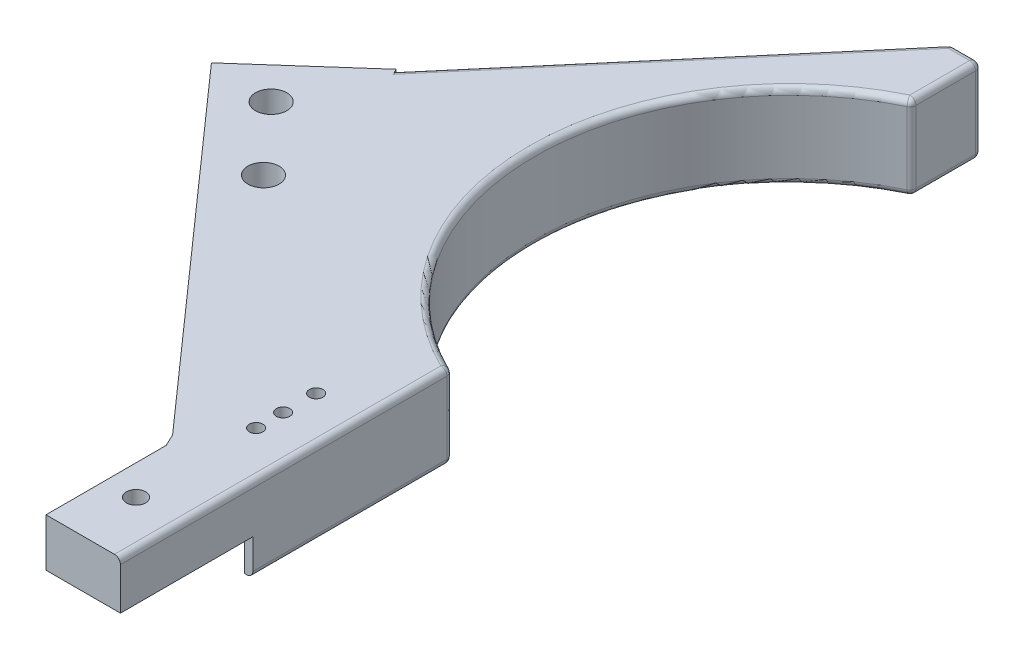
SolidWorks part; units mm, degrees
ref_plane "Front Plane" through (0, 0, 0) normal (0, 0, 1) x (1, 0, 0)
ref_plane "Top Plane" through (0, 0, 0) normal (0, 1, 0) x (1, 0, 0)
ref_plane "Right Plane" through (0, 0, 0) normal (1, 0, 0) x (0, 0, -1)
sketch "Sketch1" plane through (0, 0, 0) normal (0, 1, 0) x (1, 0, 0)
  line L0 (47.5, -78.4427) -> (47.5, -38.4427)
  line L1 (42.5, 50) -> (0, 0)
  line L2 (0, 0) -> (35.1, -73.4224)
  line L3 (47.5, 38.4427) -> (47.5, 50)
  line L4 (42.5, 50) -> (47.5, 50)
  line L6 (35.1, -73.4224) -> (35.1, -93.4427)
  line L8 (37.5, -78.4427) -> (37.5, -93.4427) construction
  line L9 (37.5, -93.4427) -> (47.5, -93.4427)
  line L10 (47.5, -78.4427) -> (47.5, -93.4427)
  line L11 (35.1, -93.4427) -> (37.5, -93.4427)
  line L12 (35.1, -73.4224) -> (37.5, -78.4427) construction
  arc A0 (47.5, 38.4427) -> (47.5, -38.4427) centre (65.622, 0) ccw
  dimension "D1" = 85
  dimension "D2" = 50
  dimension "D3" = 40
  dimension "D4" = 47.5
  dimension "D5" = 10
  dimension "D6" = 5
  dimension "D7" = 65.622
  dimension "D8" = 15
  dimension "D9" = 12.4
extrude "Boss-Extrude1" add sketch "Sketch1" along normal blind 14
sketch "Sketch3" plane through (0, 0, 0) normal (0, -1, 0) x (1, 0, 0)
  line L8 (36.1851, 83.429) -> (36.1851, 109.2435) construction
  line L9 (33.255, 84.4031) -> (36.1851, 92.429)
  line L10 (35.3457, 53.1123) -> (33.255, 84.4031)
  line L11 (46.1351, 70.029) -> (44.8209, 53.0622)
  line L12 (46.1351, 88.029) -> (46.1351, 70.029)
  line L13 (44.8851, 92.429) -> (46.1351, 88.029)
  line L14 (36.1851, 92.429) -> (44.8851, 92.429)
  circle A6 centre (40.0851, 83.429) radius 6.75 construction
  circle A7 centre (40.0851, 83.429) radius 4.125
  circle A8 centre (40.0851, 63.429) radius 1.5 construction
  circle A9 centre (40.0851, 58.929) radius 1.5 construction
  circle A10 centre (40.0851, 53.429) radius 1.5 construction
  arc A11 (44.8209, 53.0622) -> (35.3457, 53.1123) centre (40.0851, 53.429) cw
  point P48 (33.3351, 83.429)
  dimension "D6" = 108.929
  dimension "D7" = 113.429
  dimension "D1" = 3
  dimension "D2" = 40.0851
  dimension "D3" = 47.5
  dimension "D4" = 50
  dimension "D5" = 103.429
extrude "Cut-Extrude1" cut sketch "Sketch3" against normal blind 6
sketch "Sketch5" plane through (0, 6, 0) normal (0, -1, 0) x (1, 0, 0)
  circle A0 centre (40.0851, 63.429) radius 1.125
  circle A1 centre (40.0851, 58.929) radius 1.125
  circle A2 centre (40.0851, 53.429) radius 1.125
  circle A3 centre (40.0851, 63.429) radius 1.5 construction
  circle A4 centre (40.0851, 58.929) radius 1.5 construction
  circle A5 centre (40.0851, 53.429) radius 1.5 construction
  dimension "D1" = 2.25
extrude "Cut-Extrude2" cut sketch "Sketch5" against normal blind 15
fillet "Fillet1" radius 1 14 edges at (47.5, 7, 38.4427) (47.5, 7, -38.4427) (47.5, 7, -50) (42.5, 7, -50) (21.25, 14, -25) (45, 14, -50) (47.5, 14, -44.2214) (23.122, 14, 0) (47.5, 14, 65.9427) (21.25, 0, -25) (45, 0, -50) (47.5, 0, -44.2214) (23.122, 0, 0) (47.5, 0, 65.9427)
sketch "Sketch6" plane through (0, 0, 0) normal (0, -1, 0) x (1, 0, 0)
  line L0 (-40.4586, -20.0772) -> (-49.8876, -23.408)
  line L2 (0, 0) -> (34.1249, 71.3827)
  line L5 (-49.8876, -23.408) -> (34.1249, 71.3827)
  line L6 (-40.4586, -20.0772) -> (-20.5602, 2.374)
  arc A0 (0, 0) -> (-20.5602, 2.374) centre (-20.6309, -88.4563) ccw
  dimension "D1" = 10
  dimension "D2" = 30
  dimension "D3" = 16
extrude "Boss-Extrude3" add sketch "Sketch6" along normal blind 20 and the other way blind 34
sketch "Sketch7" plane through (-16.3209, 0, 14.4651) normal (-0.7484, 0, 0.6633) x (0.6633, 0, 0.7484)
  line L0 (76.0552, 14) -> (29.3477, 14)
  line L1 (76.0552, 0) -> (29.3477, 0)
  line L2 (29.3477, 34) -> (76.0552, 34)
  line L3 (76.0552, 34) -> (76.0552, 14)
  line L4 (29.3477, -20) -> (76.0552, -20)
  line L5 (76.0552, -20) -> (76.0552, 0)
  line L6 (76.0552, 34) -> (-50.6072, 34) construction
  line L7 (76.0552, 34) -> (76.0552, 14) construction
  line L8 (76.0552, 0) -> (76.0552, -20) construction
  line L9 (76.0552, -20) -> (-50.6072, -20) construction
  line L10 (29.3477, 14) -> (29.3477, 34)
  line L11 (29.3477, 0) -> (29.3477, -20)
  line L12 (1.0529, 14) -> (76.0552, 14) construction
extrude "Cut-Extrude3" cut sketch "Sketch7" against normal blind 30
sketch "Sketch10" plane through (0, -20, 0) normal (0, -1, 0) x (1, 0, 0)
  line L1 (-49.8876, -23.408) -> (-42.4038, -30.0408)
  line L2 (-49.8876, -23.408) -> (-16.7236, 14.0107)
  line L3 (-16.7236, 14.0107) -> (0, 0)
  line L4 (-42.4038, -30.0408) -> (0, 0)
  line L7 (3.1449, 36.4281) -> (-49.8876, -23.408) construction
  dimension "D1" = 10
  dimension "D2" = 90
  dimension "D3" = 50
extrude "Boss-Extrude4" add sketch "Sketch10" against normal blind 3
extrude "Boss-Extrude5" add sketch "Sketch10<2>" along normal blind 3 from surface starting at face at (-15.7543, 34, 3.9082)
sketch "Sketch10<2>" plane through (0, -20, 0) normal (0, -1, 0) x (1, 0, 0) same geometry as "Sketch10"
ref_plane "Plane2" through (0, 7, 0) normal (0, -1, 0) x (-1, 0, 0)
sketch "Sketch15" plane through (0, 6, 0) normal (0, -1, 0) x (-1, 0, 0)
  line L1 (-30.98, -71.3827) -> (-57.8606, -71.3827)
  line L2 (-30.98, -71.3827) -> (-30.98, -112.2395)
  line L3 (-30.98, -112.2395) -> (-57.8606, -112.2395)
  line L4 (-57.8606, -71.3827) -> (-57.8606, -112.2395)
extrude "Cut-Extrude5" cut sketch "Sketch15" along normal up to surface (6 mm away) up to face at (40.0851, 0, 87.554)
sketch "Sketch16" plane through (0, 14, 0) normal (0, 1, 0) x (1, 0, 0)
  circle A0 centre (40.0851, -83.429) radius 1.6
  circle A1 centre (40.0851, -63.429) radius 1.125 construction
  dimension "D1" = 20
  dimension "D2" = 3.2
extrude "Cut-Extrude6" cut sketch "Sketch16" against normal up to next
sketch "Sketch17" plane through (0, 7, 0) normal (0, -1, 0) x (-1, 0, 0)
  circle A0 centre (-22.3948, -50.6094) radius 103.4568 construction
sketch "Sketch18" plane through (0, 0, 0) normal (0.9022, 0, -0.4313) x (-0.4313, 0, -0.9022)
  line L0 (-39.632, 14) -> (0, 14)
  line L2 (-39.632, 14) -> (-42.0149, 38.6641)
  line L3 (-42.0149, 38.6641) -> (76.5332, 47.1962)
  line L4 (76.5332, 47.1962) -> (76.5332, -56.0661)
  line L5 (0, 31) -> (0, 13) construction
  line L6 (76.5332, -56.0661) -> (-34.3063, -43.9624)
  line L7 (-34.3063, -43.9624) -> (-37.3703, 0)
  line L8 (-37.3703, 0) -> (0, 0)
  line L10 (0, 0) -> (0, 14)
  line L12 (-55.3064, 0) -> (15.1951, 0) construction
  line L13 (0, 13) -> (0, 1) construction
  line L14 (-1.0954, 14) -> (-30.5304, 14) construction
extrude "Cut-Extrude7" cut sketch "Sketch18" against normal through all
sketch "Sketch19" plane through (0, 0, 0) normal (0, -1, 0) x (-1, 0, 0)
  line L0 (16.3209, -14.4651) -> (0, 0)
  line L1 (0, 0) -> (18.1152, 31.63)
  line L2 (18.1152, 31.63) -> (35.2038, 6.8403)
  line L3 (35.2038, 6.8403) -> (16.3209, -14.4651)
  line L4 (-34.1249, -71.3827) -> (20.4687, -9.7852) construction
  point P2 (0, 0)
  point P7 (0, 0)
extrude "Cut-Extrude8" cut sketch "Sketch19" against normal through all
sketch "Sketch20" plane through (0, 0, 0) normal (0, -1, 0) x (-1, 0, 0)
  line L0 (0, 0) -> (16.3209, -14.4651) construction
  line L1 (-34.1249, -71.3827) -> (16.3209, -14.4651) construction
  line L2 (5.7335, -15.1033) -> (-16.744, -40.4645) construction
  circle A0 centre (5.7335, -15.1033) radius 2.6
  circle A1 centre (-4.2157, -26.3289) radius 2.6
  point P6 (0, 0)
  dimension "D1" = 5.2
  dimension "D3" = 7.5
  dimension "D4" = 15
  dimension "D2" = 7.5
extrude "Cut-Extrude9" cut sketch "Sketch20" against normal through all
equation "\"A\"= 20mm"
equation "\"B\"= 3"
equation "\"5.000000mmB\"=5"
